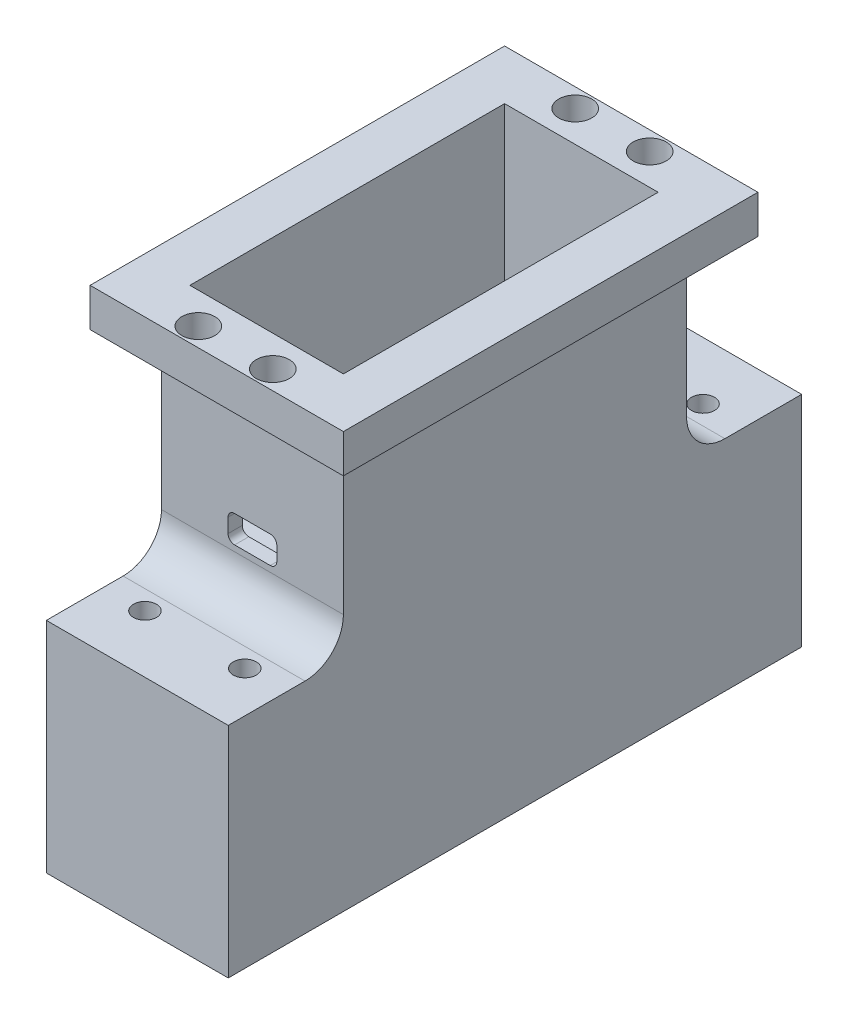
SolidWorks part; units mm, degrees
ref_plane "Front Plane" through (0, 0, 0) normal (0, 0, 1) x (1, 0, 0)
ref_plane "Top Plane" through (0, 0, 0) normal (0, 1, 0) x (1, 0, 0)
ref_plane "Right Plane" through (0, 0, 0) normal (1, 0, 0) x (0, 0, -1)
sketch "Croquis1" plane through (0, 0, 0) normal (0, 1, 0) x (1, 0, 0)
  line L0 (-16.5, 27) -> (-16.5, -27)
  line L1 (-10, 20.5) -> (10, 20.5)
  line L2 (-10, 20.5) -> (-10, -20.5)
  line L3 (-10, -20.5) -> (10, -20.5)
  line L4 (10, 20.5) -> (10, -20.5)
  line L5 (-10, 20.5) -> (10, -20.5) construction
  line L6 (-10, -20.5) -> (10, 20.5) construction
  line L7 (-16.5, -27) -> (16.5, -27)
  line L8 (16.5, 27) -> (16.5, -27)
  line L9 (-16.5, 27) -> (16.5, 27)
  line L10 (11.85, 22.35) -> (11.85, -22.35)
  line L11 (-11.85, -22.35) -> (11.85, -22.35)
  line L12 (-11.85, 22.35) -> (-11.85, -22.35)
  line L13 (-11.85, 22.35) -> (11.85, 22.35)
  point P0 (0, 0)
  dimension "D2" = 41
  dimension "D3" = 20
  dimension "D1" = 6.5
  dimension "D4" = 1.85
extrude "Saliente-Extruir1" add sketch "Croquis1" along normal blind 30.3 contours L13 L12 L11 L10 L1 L4 L3 L2 region at (11.3441, 0, 0)
extrude "Saliente-Extruir2" add sketch "Croquis1<2>" along normal blind 2 contours L4 L1 L2 L3 region at (0, 0, 0)
sketch "Croquis1<2>" plane through (0, 0, 0) normal (0, 1, 0) x (1, 0, 0) same geometry as "Croquis1"
extrude "Saliente-Extruir3" add sketch "Croquis1<4>" against normal blind 5 from surface contours L9 L0 L7 L8 L12 L13 L10 L11 region at (0, 0, -26.3671) starting at face at (0, 30.3, 0)
sketch "Croquis1<4>" plane through (0, 0, 0) normal (0, 1, 0) x (1, 0, 0) same geometry as "Croquis1"
sketch "Croquis2" plane through (0, 0, 0) normal (0, -1, 0) x (1, 0, 0)
  line L0 (-11.85, -37.35) -> (-11.85, 37.35)
  line L1 (-11.85, 22.35) -> (-11.85, -22.35) construction
  line L2 (-11.85, 37.35) -> (11.85, 37.35)
  line L3 (11.85, 37.35) -> (11.85, -37.35)
  line L4 (11.85, -22.35) -> (11.85, 22.35) construction
  line L5 (-11.85, 22.35) -> (11.85, 22.35) construction
  line L6 (-11.85, 0) -> (11.85, 0) construction
  line L7 (-11.85, -37.35) -> (11.85, -37.35)
  circle A0 centre (-6.5, 29.85) radius 1.5
  circle A1 centre (6.5, 29.85) radius 1.5
  circle A2 centre (6.5, -29.85) radius 1.5
  circle A3 centre (-6.5, -29.85) radius 1.5
  point P15 (0, 37.35)
  dimension "D3" = 3
  dimension "D2" = 15
  dimension "D5" = 6.5
  dimension "D6" = 6.5
  dimension "D7" = 7.5
extrude "Saliente-Extruir5" add sketch "Croquis2" along normal blind 28.5
fillet "Redondeo2" radius 5 2 edges at (0, 0, 22.35) (0, 0, -22.35)
sketch "Croquis3" plane through (0, 0, 22.35) normal (0, 0, 1) x (1, 0, 0)
  line L0 (-2.325, 9.325) -> (2.325, 9.325)
  line L1 (3.175, 8.475) -> (3.175, 6.625)
  line L2 (2.325, 5.775) -> (-2.325, 5.775)
  line L3 (-3.175, 6.625) -> (-3.175, 8.475)
  arc A0 (2.325, 9.325) -> (3.175, 8.475) centre (2.325, 8.475) cw
  arc A1 (3.175, 6.625) -> (2.325, 5.775) centre (2.325, 6.625) cw
  arc A2 (-2.325, 5.775) -> (-3.175, 6.625) centre (-2.325, 6.625) cw
  arc A3 (-3.175, 8.475) -> (-2.325, 9.325) centre (-2.325, 8.475) cw
  point P20 (3.175, 7.55)
  point P22 (0, 9.325)
  dimension "D2" = 0.85
  dimension "D1" = 7.55
  dimension "D3" = 6.35
  dimension "D4" = 3.55
extrude "Cortar-Extruir1" cut sketch "Croquis3" against normal mid plane 10
sketch "Croquis4" plane through (0, 30.3, 0) normal (0, 1, 0) x (1, 0, 0)
  line L0 (0, -0.25) -> (25.4131, -0.25) construction
  line L1 (0, -0.25) -> (0, 11.0993) construction
  circle A0 centre (-4.85, 24.55) radius 2.15
  arc A1 (-1.75, 1.5) -> (1.75, 1.5) centre (0, 1.5) ccw construction
  circle A2 centre (4.85, 24.55) radius 2.15
  circle A5 centre (-4.85, -24.55) radius 2.15
  circle A6 centre (4.85, -24.55) radius 2.15
  dimension "D1" = 4.3
  dimension "D2" = 4.3
extrude "Cortar-Extruir2" cut sketch "Croquis4" against normal blind 10
